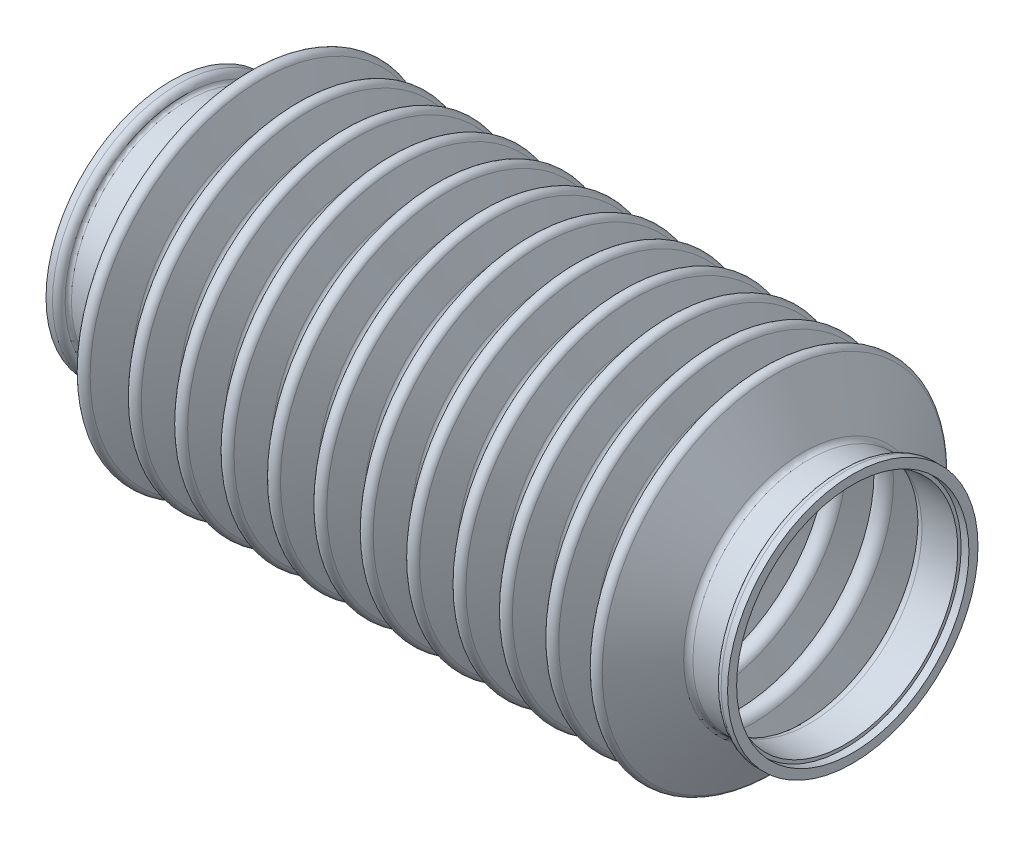
SolidWorks part; units mm, degrees
ref_plane "Alzado" through (0, 0, 0) normal (0, 0, 1) x (1, 0, 0)
ref_plane "Planta" through (0, 0, 0) normal (0, 1, 0) x (1, 0, 0)
ref_plane "Vista lateral" through (0, 0, 0) normal (1, 0, 0) x (0, 0, -1)
sketch "Croquis1" plane through (0, 0, 0) normal (0, 0, 1) x (1, 0, 0)
  line L0 (-66.1214, 37.7921) -> (-66.1214, 35.0586)
  line L1 (-62.1717, 0) -> (100.9562, 0) construction
  line L2 (-61.1836, 35.0586) -> (-52.9347, 35.0586)
  line L3 (-51.1833, 36.0929) -> (-42.4423, 51.9452)
  line L4 (-38.8423, 51.7426) -> (-35.1248, 42.7368)
  line L5 (-24.4274, 50.7375) -> (-21.1248, 42.7368)
  line L6 (-28.1248, 50.7375) -> (-31.4274, 42.7368)
  line L7 (-14.1248, 50.7375) -> (-17.4274, 42.7368)
  line L8 (-10.4274, 50.7375) -> (-7.1248, 42.7368)
  line L9 (-0.1248, 50.7375) -> (-3.4274, 42.7368)
  line L10 (3.5726, 50.7375) -> (6.8752, 42.7368)
  line L11 (13.8752, 50.7375) -> (10.5726, 42.7368)
  line L12 (17.5726, 50.7375) -> (20.8752, 42.7368)
  line L13 (27.8752, 50.7375) -> (24.5726, 42.7368)
  line L14 (31.5726, 50.7375) -> (34.8752, 42.7368)
  line L15 (-64.1717, 37.7921) -> (-66.1214, 37.7921)
  line L16 (-61.1836, 34.0586) -> (-52.9347, 34.0586)
  line L17 (-50.3076, 35.6101) -> (-41.5666, 51.4623)
  line L18 (43.5686, 55.5922) -> (50.7239, 38.2584) [skipped]
  line L19 (57.8792, 55.5922) -> (50.7239, 38.2584) [skipped]
  line L20 (43.8792, 55.5922) -> (38.5726, 42.7368) [skipped]
  line L21 (-39.7666, 51.361) -> (-36.0491, 42.3553)
  line L22 (-27.2004, 50.356) -> (-30.503, 42.3553)
  line L23 (-25.3517, 50.356) -> (-22.0491, 42.3553)
  line L24 (-13.2004, 50.356) -> (-16.503, 42.3553)
  line L25 (-11.3517, 50.356) -> (-8.0491, 42.3553)
  line L26 (0.7996, 50.356) -> (-2.503, 42.3553)
  line L27 (2.6483, 50.356) -> (5.9509, 42.3553)
  line L28 (14.7996, 50.356) -> (11.497, 42.3553)
  line L29 (16.6483, 50.356) -> (19.9509, 42.3553)
  line L30 (28.7996, 50.356) -> (25.497, 42.3553)
  line L31 (30.6483, 50.356) -> (33.9509, 42.3553)
  line L32 (-64.1717, 36.7921) -> (-66.1214, 36.7921) construction
  line L33 (-66.1214, 35.0586) -> (-63.7677, 35.0586)
  line L34 (-63.7677, 35.0586) -> (-63.7677, 34.0586)
  line L35 (-63.7677, 34.0586) -> (-61.1836, 34.0586)
  line L36 (36.7239, 46.4242) -> (36.7239, 34.7599) construction
  line L37 (137.2155, 34.0586) -> (134.6315, 34.0586)
  line L38 (137.2155, 35.0586) -> (137.2155, 34.0586)
  line L39 (139.5692, 35.0586) -> (137.2155, 35.0586)
  line L40 (70.7996, 50.356) -> (67.497, 42.3553)
  line L41 (72.6483, 50.356) -> (75.9509, 42.3553)
  line L42 (84.7996, 50.356) -> (81.497, 42.3553)
  line L43 (86.6483, 50.356) -> (89.9509, 42.3553)
  line L44 (98.7996, 50.356) -> (95.497, 42.3553)
  line L45 (100.6483, 50.356) -> (103.9509, 42.3553)
  line L46 (113.2145, 51.361) -> (109.497, 42.3553)
  line L47 (123.7555, 35.6101) -> (115.0145, 51.4623)
  line L48 (134.6315, 34.0586) -> (126.3826, 34.0586)
  line L49 (137.6196, 37.7921) -> (139.5692, 37.7921)
  line L50 (69.8752, 50.7375) -> (66.5726, 42.7368)
  line L51 (73.5726, 50.7375) -> (76.8752, 42.7368)
  line L52 (83.8752, 50.7375) -> (80.5726, 42.7368)
  line L53 (87.5726, 50.7375) -> (90.8752, 42.7368)
  line L54 (101.5726, 50.7375) -> (104.8752, 42.7368)
  line L55 (97.8752, 50.7375) -> (94.5726, 42.7368)
  line L56 (112.2901, 51.7426) -> (108.5726, 42.7368)
  line L57 (124.6312, 36.0929) -> (115.8902, 51.9452)
  line L58 (134.6315, 35.0586) -> (126.3826, 35.0586)
  line L59 (139.5692, 37.7921) -> (139.5692, 35.0586)
  line L60 (58.6483, 50.356) -> (61.9509, 42.3553)
  line L61 (59.5726, 50.7375) -> (62.8752, 42.7368)
  line L62 (42.7996, 50.356) -> (39.497, 42.3553)
  line L63 (44.6483, 50.356) -> (47.9509, 42.3553)
  line L64 (56.7996, 50.356) -> (53.497, 42.3553)
  line L65 (41.8752, 50.7375) -> (38.5726, 42.7368)
  line L66 (45.5726, 50.7375) -> (48.8752, 42.7368)
  line L67 (55.8752, 50.7375) -> (52.5726, 42.7368)
  arc A0 (-38.8423, 51.7426) -> (-42.4423, 51.9452) centre (-40.6909, 50.9794) ccw
  arc A1 (-31.4274, 42.7368) -> (-35.1248, 42.7368) centre (-33.2761, 43.5) cw
  arc A2 (-24.4274, 50.7375) -> (-28.1248, 50.7375) centre (-26.2761, 49.9744) ccw
  arc A3 (-17.4274, 42.7368) -> (-21.1248, 42.7368) centre (-19.2761, 43.5) cw
  arc A4 (-10.4274, 50.7375) -> (-14.1248, 50.7375) centre (-12.2761, 49.9744) ccw
  arc A5 (-3.4274, 42.7368) -> (-7.1248, 42.7368) centre (-5.2761, 43.5) cw
  arc A6 (3.5726, 50.7375) -> (-0.1248, 50.7375) centre (1.7239, 49.9744) ccw
  arc A7 (10.5726, 42.7368) -> (6.8752, 42.7368) centre (8.7239, 43.5) cw
  arc A8 (17.5726, 50.7375) -> (13.8752, 50.7375) centre (15.7239, 49.9744) ccw
  arc A9 (24.5726, 42.7368) -> (20.8752, 42.7368) centre (22.7239, 43.5) cw
  arc A10 (31.5726, 50.7375) -> (27.8752, 50.7375) centre (29.7239, 49.9744) ccw
  arc A11 (36.7239, 41.5) -> (34.8752, 42.7368) centre (36.7239, 43.5) cw
  arc A12 (-51.1833, 36.0929) -> (-52.9347, 35.0586) centre (-52.9347, 37.0586) cw
  arc A13 (-62.1796, 35.9698) -> (-64.1717, 37.7921) centre (-64.1717, 35.7921) ccw
  arc A14 (-61.1836, 35.0586) -> (-62.1796, 35.9698) centre (-61.1836, 36.0586) cw
  arc A15 (70.7996, 50.356) -> (72.6483, 50.356) centre (71.7239, 49.9744) cw
  arc A16 (75.9509, 42.3553) -> (81.497, 42.3553) centre (78.7239, 43.5) ccw
  arc A17 (-50.3076, 35.6101) -> (-52.9347, 34.0586) centre (-52.9347, 37.0586) cw
  arc A18 (-39.7666, 51.361) -> (-41.5666, 51.4623) centre (-40.6909, 50.9794) ccw
  arc A19 (-30.503, 42.3553) -> (-36.0491, 42.3553) centre (-33.2761, 43.5) cw
  arc A20 (-25.3517, 50.356) -> (-27.2004, 50.356) centre (-26.2761, 49.9744) ccw
  arc A21 (-16.503, 42.3553) -> (-22.0491, 42.3553) centre (-19.2761, 43.5) cw
  arc A22 (-11.3517, 50.356) -> (-13.2004, 50.356) centre (-12.2761, 49.9744) ccw
  arc A23 (-2.503, 42.3553) -> (-8.0491, 42.3553) centre (-5.2761, 43.5) cw
  arc A24 (2.6483, 50.356) -> (0.7996, 50.356) centre (1.7239, 49.9744) ccw
  arc A25 (11.497, 42.3553) -> (5.9509, 42.3553) centre (8.7239, 43.5) cw
  arc A26 (16.6483, 50.356) -> (14.7996, 50.356) centre (15.7239, 49.9744) ccw
  arc A27 (25.497, 42.3553) -> (19.9509, 42.3553) centre (22.7239, 43.5) cw
  arc A28 (30.6483, 50.356) -> (28.7996, 50.356) centre (29.7239, 49.9744) ccw
  arc A29 (36.7239, 40.5) -> (33.9509, 42.3553) centre (36.7239, 43.5) cw
  arc A30 (-61.1836, 34.0586) -> (-63.1757, 35.881) centre (-61.1836, 36.0586) cw construction
  arc A31 (-63.1757, 35.881) -> (-64.1717, 36.7921) centre (-64.1717, 35.7921) ccw construction
  arc A32 (84.7996, 50.356) -> (86.6483, 50.356) centre (85.7239, 49.9744) cw
  arc A33 (89.9509, 42.3553) -> (95.497, 42.3553) centre (92.7239, 43.5) ccw
  arc A34 (98.7996, 50.356) -> (100.6483, 50.356) centre (99.7239, 49.9744) cw
  arc A35 (103.9509, 42.3553) -> (109.497, 42.3553) centre (106.7239, 43.5) ccw
  arc A36 (113.2145, 51.361) -> (115.0145, 51.4623) centre (114.1388, 50.9794) cw
  arc A37 (123.7555, 35.6101) -> (126.3826, 34.0586) centre (126.3826, 37.0586) ccw
  arc A38 (134.6315, 35.0586) -> (135.6275, 35.9698) centre (134.6315, 36.0586) ccw
  arc A39 (135.6275, 35.9698) -> (137.6196, 37.7921) centre (137.6196, 35.7921) cw
  arc A40 (124.6312, 36.0929) -> (126.3826, 35.0586) centre (126.3826, 37.0586) ccw
  arc A41 (69.8752, 50.7375) -> (73.5726, 50.7375) centre (71.7239, 49.9744) cw
  arc A42 (76.8752, 42.7368) -> (80.5726, 42.7368) centre (78.7239, 43.5) ccw
  arc A43 (83.8752, 50.7375) -> (87.5726, 50.7375) centre (85.7239, 49.9744) cw
  arc A44 (90.8752, 42.7368) -> (94.5726, 42.7368) centre (92.7239, 43.5) ccw
  arc A45 (97.8752, 50.7375) -> (101.5726, 50.7375) centre (99.7239, 49.9744) cw
  arc A46 (104.8752, 42.7368) -> (108.5726, 42.7368) centre (106.7239, 43.5) ccw
  arc A47 (112.2901, 51.7426) -> (115.8902, 51.9452) centre (114.1388, 50.9794) cw
  arc A48 (56.7996, 50.356) -> (58.6483, 50.356) centre (57.7239, 49.9744) cw
  arc A49 (61.9509, 42.3553) -> (67.497, 42.3553) centre (64.7239, 43.5) ccw
  arc A50 (55.8752, 50.7375) -> (59.5726, 50.7375) centre (57.7239, 49.9744) cw
  arc A51 (62.8752, 42.7368) -> (66.5726, 42.7368) centre (64.7239, 43.5) ccw
  arc A52 (42.7996, 50.356) -> (44.6483, 50.356) centre (43.7239, 49.9744) cw
  arc A53 (41.8752, 50.7375) -> (45.5726, 50.7375) centre (43.7239, 49.9744) cw
  arc A54 (36.7239, 40.5) -> (39.497, 42.3553) centre (36.7239, 43.5) ccw
  arc A55 (47.9509, 42.3553) -> (53.497, 42.3553) centre (50.7239, 43.5) ccw
  arc A56 (36.7239, 41.5) -> (38.5726, 42.7368) centre (36.7239, 43.5) ccw
  arc A57 (48.8752, 42.7368) -> (52.5726, 42.7368) centre (50.7239, 43.5) ccw
  dimension "D1" = 2
  dimension "D2" = 2
  dimension "D3" = 2
  dimension "D4" = 1
  dimension "D5" = 1
revolve "Revolución1" add sketch "Croquis1" angle 360 about L1
